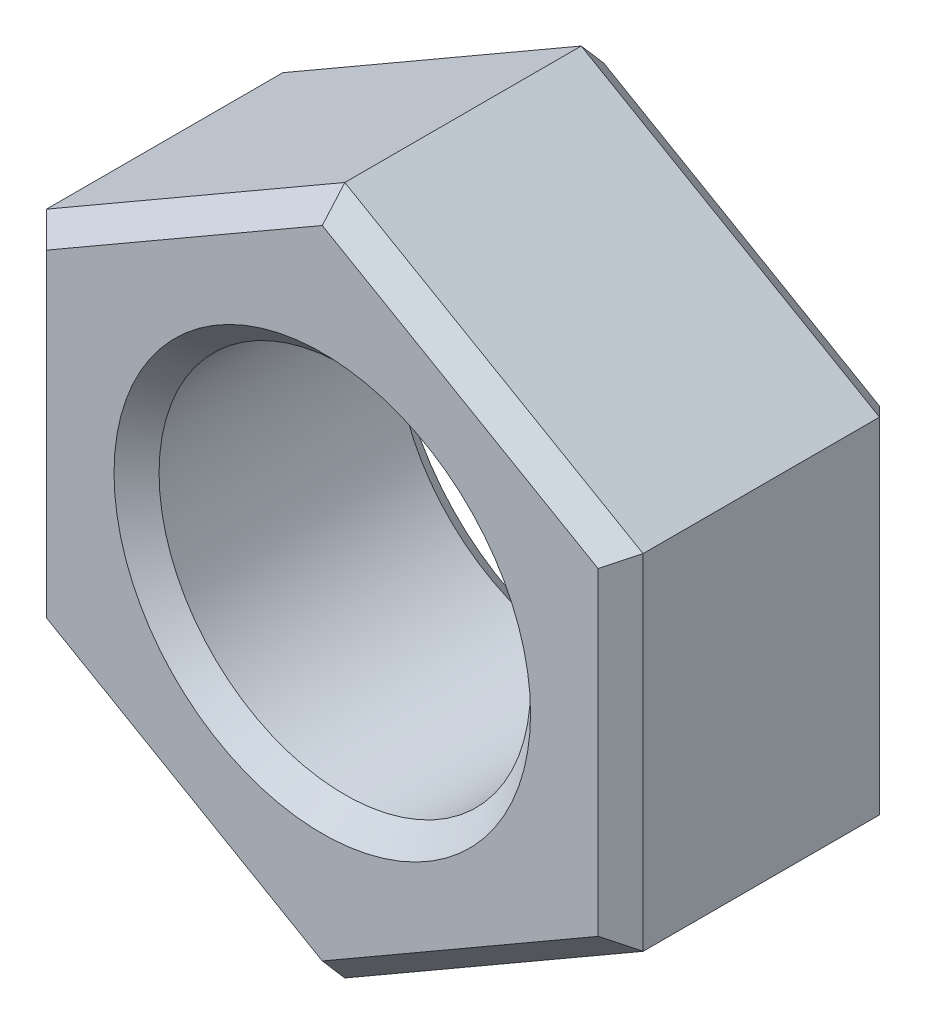
SolidWorks part; units mm, degrees
ref_plane "Front" through (0, 0, 0) normal (0, 0, 1) x (1, 0, 0)
ref_plane "Top" through (0, 0, 0) normal (0, 1, 0) x (1, 0, 0)
ref_plane "Right" through (0, 0, 0) normal (1, 0, 0) x (0, 0, -1)
sketch "Sketch1" plane through (0, 0, 0) normal (0, 0, 1) x (1, 0, 0)
  line L1 (2.65, -1.53) -> (2.65, 1.53)
  line L2 (2.65, 1.53) -> (0, 3.06)
  line L3 (0, 3.06) -> (-2.65, 1.53)
  line L4 (-2.65, 1.53) -> (-2.65, -1.53)
  line L5 (-2.65, -1.53) -> (0, -3.06)
  line L6 (0, -3.06) -> (2.65, -1.53)
  circle A0 centre (0, 0) radius 2.65 construction
  circle A1 centre (0, 0) radius 1.65
  dimension "D1" = 3.3
  dimension "D2" = 5.3
extrude "Boss-Extrude1" add sketch "Sketch1" along normal mid plane 2.5
chamfer "Deburs" distance 0.2 angle 45 14 edges at (1.65, 0, -1.25) (2.65, 0, -1.25) (1.325, 2.295, -1.25) (-1.325, 2.295, -1.25) (-2.65, 0, -1.25) (-1.325, -2.295, -1.25) (1.325, -2.295, -1.25) (1.65, 0, 1.25) (-1.325, -2.295, 1.25) (-2.65, 0, 1.25) (-1.325, 2.295, 1.25) (1.325, 2.295, 1.25) (2.65, 0, 1.25) (1.325, -2.295, 1.25)
equation "\"D1@Sketch1\"=\"Hardware Clearance Hole Diameter@Box Assy.Assembly\"+.15"
equation "\"D2@Sketch1\"=\"Nut Trap Diameter@Box Assy.Assembly\"-0.3mm"
equation "\"D1@Boss-Extrude1\"=\"Nut Trap Depth@Box Assy.Assembly\""
